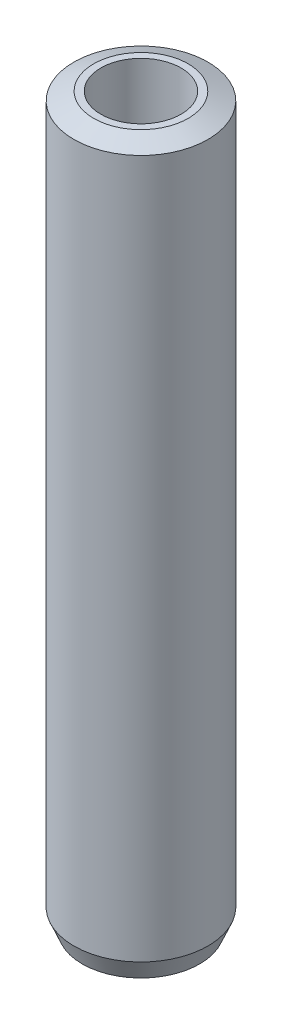
SolidWorks part; units mm, degrees
ref_plane "Front Plane" through (0, 0, 0) normal (0, 0, 1) x (1, 0, 0)
ref_plane "Top Plane" through (0, 0, 0) normal (0, 1, 0) x (1, 0, 0)
ref_plane "Right Plane" through (0, 0, 0) normal (1, 0, 0) x (0, 0, -1)
sketch "Sketch1" plane through (0, 0, 0) normal (0, 1, 0) x (1, 0, 0)
  circle A0 centre (0, 0) radius 17.5
  dimension "SHAFT_OD" = 35
extrude "Boss-Extrude1" add sketch "Sketch1" along normal blind 189.6162
sketch "Sketch2" plane through (0, 0, 0) normal (0, 1, 0) x (1, 0, 0)
  circle A0 centre (0, 0) radius 10.4717
  dimension "BORE_D" = 20.9435
extrude "Cut-Extrude1" cut sketch "Sketch2" along normal through all
chamfer "Chamfer1" distance 2.1825 angle 67.079 2 edges at (0, 189.6162, 17.5) (0, 0, 17.5) first distance on face at (0, 189.6162, 17.5) first distance on face at (0, 0, 10.4717)
